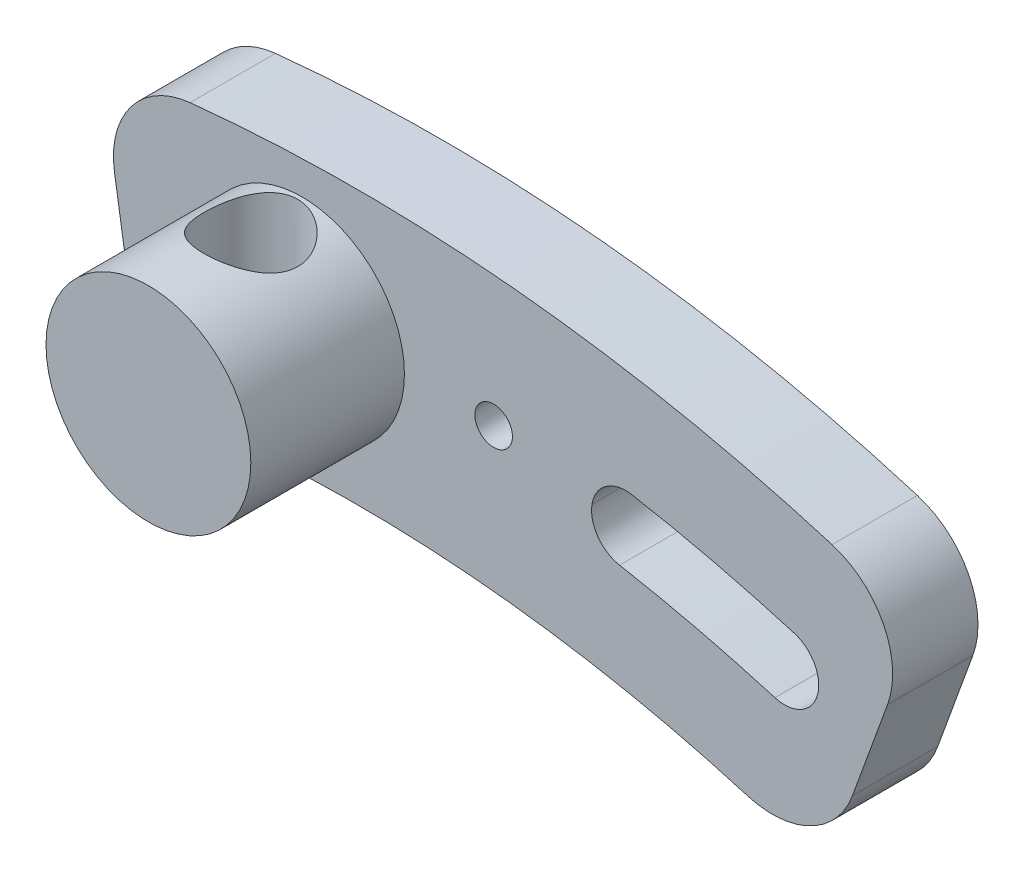
SolidWorks part; units mm, degrees
ref_plane "Front Plane" through (0, 0, 0) normal (0, 0, 1) x (1, 0, 0)
ref_plane "Top Plane" through (0, 0, 0) normal (0, 1, 0) x (1, 0, 0)
ref_plane "Right Plane" through (0, 0, 0) normal (1, 0, 0) x (0, 0, -1)
sketch "Sketch1" plane through (0, 0, 0) normal (0, 0, 1) x (1, 0, 0)
  line L0 (0, 0) -> (0, 80) construction
  line L1 (0, 0) -> (32.8339, 90.2105) construction
  line L2 (0, 0) -> (-6.116, 6.116) construction
  line L5 (27.3616, 75.1754) -> (32.8339, 90.2105)
  line L6 (0, 0) -> (-15.0177, 94.8181) construction
  line L7 (0, 0) -> (15.0177, 94.8181) construction
  line L8 (27.5717, 85.6726) -> (26.3463, 81.865)
  line L9 (0, 0) -> (25.144, 82.2422) construction
  line L10 (-15.0177, 94.8181) -> (-12.5148, 79.0151)
  line L11 (15.0177, 94.8181) -> (12.5148, 79.0151)
  line L14 (-13.9378, 88) -> (8, 88) construction
  line L15 (-0.5, 95.9987) -> (-0.5, 79.9984)
  line L23 (0, 0) -> (-53.662, 92.9453) construction
  line L44 (44.4908, 78.2349) -> (44.4904, 78.2343)
  line L45 (44.4882, 78.2355) -> (44.4908, 78.2349)
  line L58 (22.7288, 87.0833) -> (22.7287, 87.0828)
  arc A2 (27.3616, 75.1754) -> (-12.5148, 79.0151) centre (0, 0) ccw
  arc A3 (29.4137, 80.8136) -> (13.4534, 84.9412) centre (0, 0) ccw
  arc A4 (30.7818, 84.5723) -> (14.0791, 88.892) centre (0, 0) ccw
  arc A5 (32.8339, 90.2105) -> (-15.0177, 94.8181) centre (0, 0) ccw
  circle A8 centre (-3.227, 88) radius 6
  circle A10 centre (8, 88) radius 1.1
  point P28 (-30.0281, 84.7967)
  point P40 (-22.5352, 87.1334)
  point P45 (-14.8562, 88.766)
  point P55 (-44.3168, 78.3334)
  point P68 (44.3168, 78.3334)
  point P79 (14.8562, 88.766)
  point P80 (22.5352, 87.1334)
  point P81 (30.0281, 84.7967)
  point P106 (0, 0)
  point P169 (0, 0)
  dimension "D1" = 192
  dimension "D2" = 180
  dimension "D3" = 172
  dimension "D4" = 160
  dimension "D10" = 2.2
  dimension "D6" = 12
  dimension "D5" = 20
  dimension "D7" = 9
  dimension "D8" = 50
  dimension "D11" = 8
  dimension "D13" = 3
extrude "Boss-Extrude1" add sketch "Sketch1" along normal blind 5 contours A5 L10 A2 L5
extrude "Cut-Extrude2" cut sketch "Sketch1<13>" along normal blind 10 contours L8 A4 L11 A3 | A10 region at (20.4066, 85.5271, 0)
sketch "Sketch1<13>" plane through (0, 0, 0) normal (0, 0, 1) x (1, 0, 0) same geometry as "Sketch1"
fillet "Fillet1" radius 2 4 edges at (26.3463, 81.865, 2.5) (27.5717, 85.6726, 2.5) (14.0791, 88.892, 2.5) (13.4534, 84.9412, 2.5)
extrude "Boss-Extrude2" add sketch "Sketch1<14>" along normal blind 14 contours L15 A8 | L15 A8 region at (-4.3821, 88, 0) region at (0.8456, 88, 0)
sketch "Sketch1<14>" plane through (0, 0, 0) normal (0, 0, 1) x (1, 0, 0) same geometry as "Sketch1"
sketch "Sketch2" plane through (0, 0, 0) normal (0, 1, 0) x (1, 0, 0)
  line L0 (-3.227, -14) -> (-3.227, -5) construction
  line L1 (-9.227, -5) -> (2.773, -5) construction
  line L2 (-9.227, -5) -> (2.773, -5)
  circle A0 centre (-3.227, -8) radius 1.35
  circle A1 centre (-3.227, -8) radius 2.75
  dimension "D1" = 2.7
  dimension "D3" = 5.5
  dimension "D2" = 3
extrude "Cut-Extrude3" cut sketch "Sketch2" along normal blind 110 contours A0 region at (-3.227, 0, 8)
fillet "Fillet2" radius 5 4 edges at (27.3616, 75.1754, 2.5) (32.8339, 90.2105, 2.5) (-12.5148, 79.0151, 2.5) (-15.0177, 94.8181, 2.5)
extrude "Cut-Extrude4" cut sketch "Sketch2<3>" against normal blind 111 from offset 200 contours A1
sketch "Sketch2<3>" plane through (0, 0, 0) normal (0, 1, 0) x (1, 0, 0) same geometry as "Sketch2"
